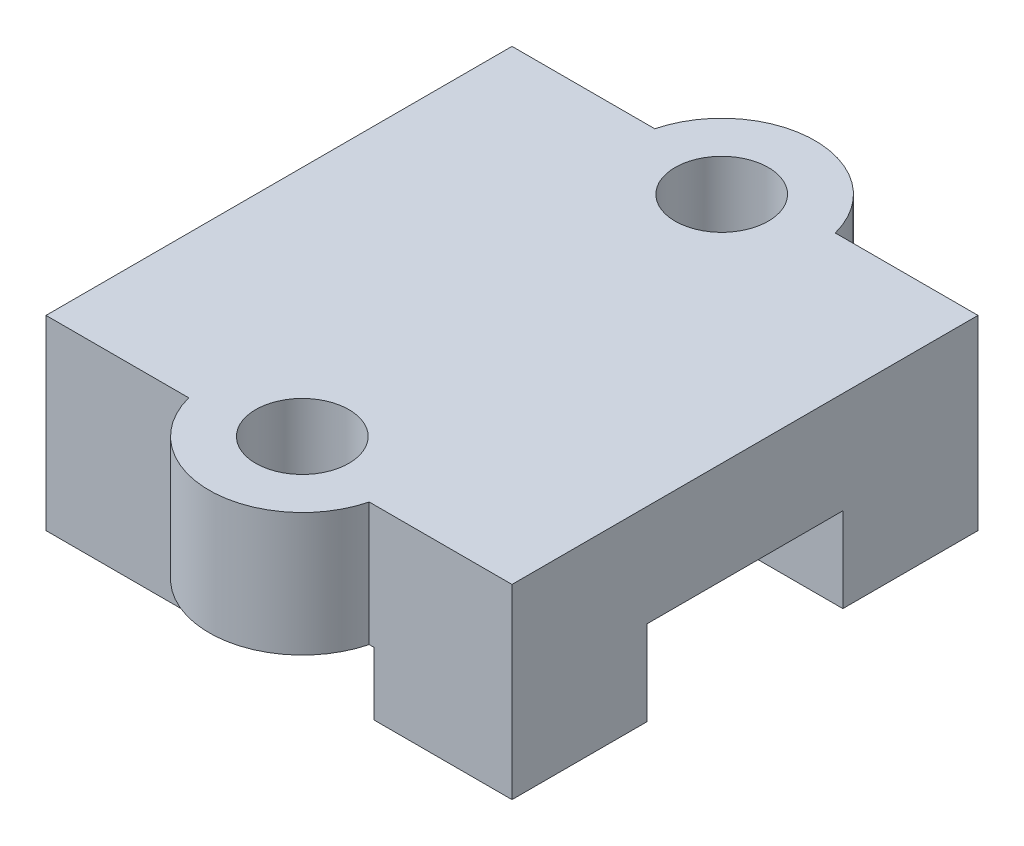
SolidWorks part; units mm, degrees
material "ABS"
ref_plane "Спереди" through (0, 0, 0) normal (0, 0, 1) x (1, 0, 0)
ref_plane "Сверху" through (0, 0, 0) normal (0, 1, 0) x (1, 0, 0)
ref_plane "Справа" through (0, 0, 0) normal (1, 0, 0) x (0, 0, -1)
sketch "Эскиз1" plane through (-110, 0, 0) normal (1, 0, 0) x (0, 0, -1)
  line L0 (-4.2, -5) -> (-4.2, -1.3625)
  line L1 (-4.2, -1.3625) -> (4.2, -1.3625)
  line L2 (4.2, -1.3625) -> (4.2, -5)
  line L3 (4.2, -5) -> (10, -5)
  line L4 (10, -5) -> (10, -6) construction
  line L5 (4.1, -5) -> (10, -5) construction
  line L6 (10, -5) -> (10, 3)
  line L7 (10, 3) -> (-10, 3)
  line L8 (-10, 3) -> (-10, -5)
  line L9 (-10, -5) -> (-4.2, -5)
  line L10 (4, -1.5625) -> (0.6, -1.5625) construction
  line L11 (-4.2, -5.722) -> (-4.2, -0.6102) construction
  line L12 (4.2, -5.722) -> (4.2, -1.1156) construction
  dimension "D1" = 0.2
  dimension "D2" = 8
extrude "Бобышка-Вытянуть1" add sketch "Эскиз1" along normal blind 10 and the other way blind 10
sketch "Эскиз3" plane through (0, 3, 0) normal (0, 1, 0) x (1, 0, 0)
  line L0 (-110, -11) -> (-110, 11) construction
  line L1 (-120, -10) -> (-100, -10) construction
  line L2 (-120, 10) -> (-100, 10) construction
  circle A0 centre (-110, -9) radius 4
  circle A1 centre (-110, 9) radius 4
  dimension "D1" = 8
  dimension "D2" = 8
  dimension "D3" = 1
  dimension "D4" = 1
extrude "Бобышка-Вытянуть2" add sketch "Эскиз3" against normal through all
sketch "Эскиз2" plane through (0, 3, 0) normal (0, 1, 0) x (1, 0, 0)
  line L0 (-110, -16.7095) -> (-110, 16.7095) construction
  line L1 (-65, -4.1) -> (-155, -4.1) construction
  line L2 (-155, -10) -> (-153.375, -10) construction
  line L3 (-120, -10) -> (-113.873, -10) construction
  line L4 (-120, 10) -> (-113.873, 10) construction
  circle A0 centre (-110, -9) radius 2
  circle A1 centre (-110, 9) radius 2
  dimension "D1" = 4
  dimension "D2" = 4
  dimension "D3" = 5.9
  dimension "D4" = 1
  dimension "D5" = 1
extrude "Вырез-Вытянуть1" cut sketch "Эскиз2" against normal blind 10
sketch "Эскиз4" plane through (0, -5, 0) normal (0, -1, 0) x (1, 0, 0)
  circle A0 centre (-110, 9) radius 2
  circle A1 centre (-110, 9) radius 4.2
  circle A2 centre (-110, -9) radius 2
  circle A3 centre (-110, -9) radius 4.2
  dimension "D1" = 8.4
  dimension "D2" = 8.4
extrude "Вырез-Вытянуть2" cut sketch "Эскиз4" against normal blind 2.7
